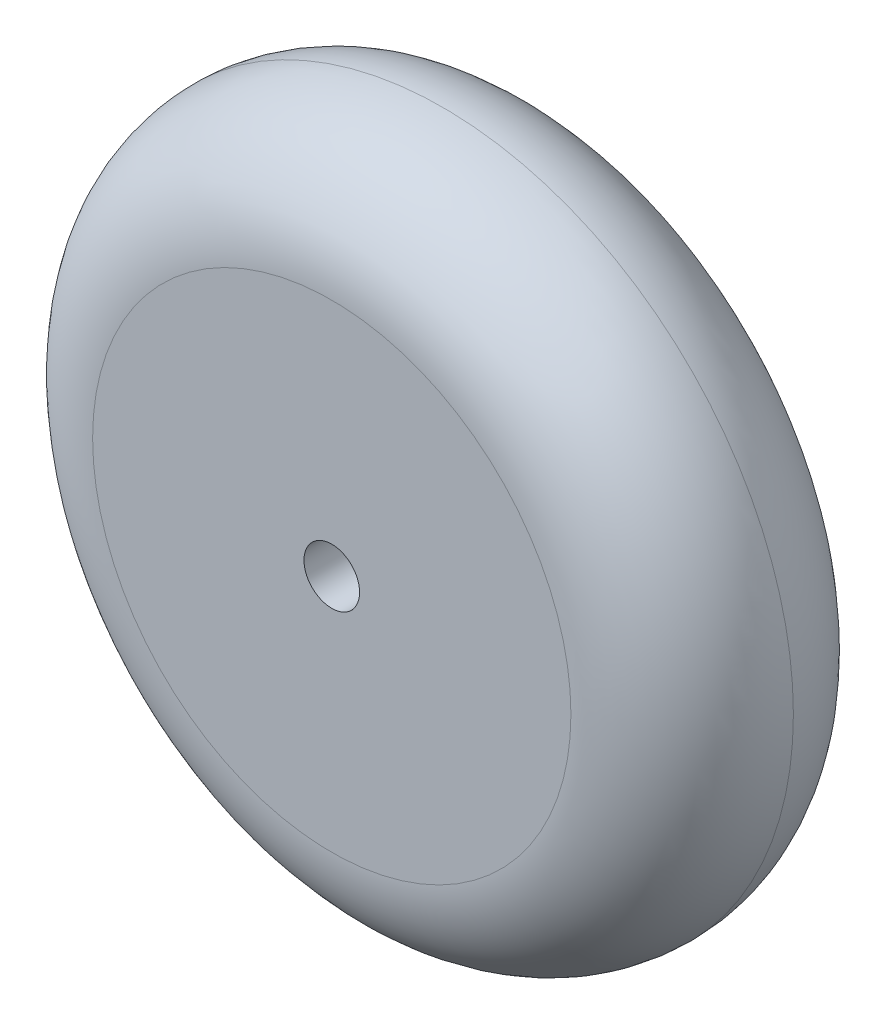
SolidWorks part; units mm, degrees
ref_plane "Front Plane" through (0, 0, 0) normal (0, 0, 1) x (1, 0, 0)
ref_plane "Top Plane" through (0, 0, 0) normal (0, 1, 0) x (1, 0, 0)
ref_plane "Right Plane" through (0, 0, 0) normal (1, 0, 0) x (0, 0, -1)
sketch "Sketch1" plane through (0, 0, 0) normal (0, 0, 1) x (1, 0, 0)
  circle A0 centre (0, 0) radius 40.005
  dimension "D1" = 80.01
extrude "Boss-Extrude1" add sketch "Sketch1" along normal blind 25.4
sketch "Sketch2" plane through (0, 0, 25.4) normal (0, 0, 1) x (1, 0, 0)
  circle A0 centre (0, 0) radius 3.175
  dimension "D1" = 6.35
extrude "Cut-Extrude1" cut sketch "Sketch2" against normal up to next
fillet "Fillet1" radius 12.7 2 edges at (40.005, 0, 0) (40.005, 0, 25.4)
